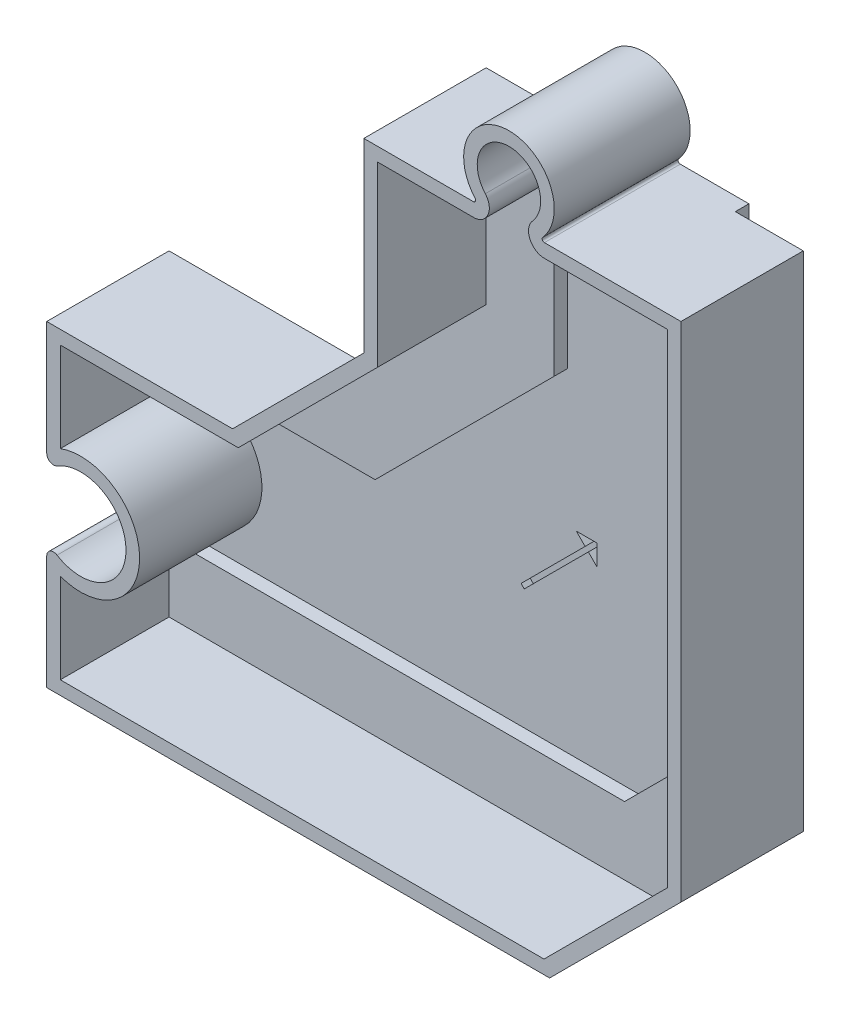
SolidWorks part; units mm, degrees
note: '?' marks a value the reader was unsure of.
material "ABS"
ref_plane "Plan de face" through (0, 0, 0) normal (0, 0, 1) x (1, 0, 0)
ref_plane "Plan de dessus" through (0, 0, 0) normal (0, 1, 0) x (1, 0, 0)
ref_plane "Plan de droite" through (0, 0, 0) normal (1, 0, 0) x (0, 0, -1)
sketch "Esquisse1" plane through (0, 0, 0) normal (0, 0, 1) x (1, 0, 0)
  line L0 (-32.0283, 105) -> (37.9717, 105)
  line L1 (37.9717, 105) -> (37.9717, -35)
  line L2 (37.9717, -35) -> (-102.0283, -35)
  line L3 (-102.0283, -35) -> (-102.0283, 35)
  line L4 (-102.0283, 35) -> (-32.0283, 35)
  line L5 (-32.0283, 35) -> (-32.0283, 105)
  line L6 (0, 105) -> (0, 0) construction
  line L7 (0, 0) -> (-102.0283, 0) construction
  dimension "D1" = 140
  dimension "D2" = 70
extrude "Boss.-Extru.1" add sketch "Esquisse1" along normal blind 30
chamfer "Chanfrein1" distance 28.99 angle 45 1 edges at (37.9717, -35, 15)
chamfer "Chanfrein2" distance 28.97 angle 45 1 edges at (-32.0283, 35, 15)
sketch3d "Esquisse3D3"
  line L0 (-87.0283, -20, 0) -> (2.7685, -20, 0)
  line L1 (-87.0283, 20, 0) -> (-87.0283, -20, 0)
  line L2 (-54.7851, 20, 0) -> (-87.0283, 20, 0)
  line L3 (-54.7851, 20, 0) -> (-17.0283, 57.7568, 0)
  line L4 (-17.0283, 90, 0) -> (-17.0283, 57.7568, 0)
  line L5 (22.9717, 90, 0) -> (-17.0283, 90, 0)
  line L6 (22.9717, 0.2032, 0) -> (22.9717, 90, 0)
  line L7 (22.9717, 0.2032, 0) -> (2.7685, -20, 0)
  line L8 (-102.0283, -20, 0) -> (2.7685, -20, 0)
  line L10 (-54.7851, 20, 0) -> (-102.0283, 20, 0)
  line L11 (-54.7851, 20, 0) -> (-17.0283, 57.7568, 0)
  line L12 (-17.0283, 105, 0) -> (-17.0283, 57.7568, 0)
  line L14 (22.9717, 0.2032, 0) -> (22.9717, 105, 0)
  line L15 (22.9717, 0.2032, 0) -> (2.7685, -20, 0)
  line L16 (-102.0283, 35, 0) -> (-102.0283, -35, 0) construction
  line L17 (37.9717, 105, 0) -> (-32.0283, 105, 0) construction
  line L18 (22.9717, 105, 0) -> (37.9717, 105, 0)
  line L19 (37.9717, 105, 0) -> (37.9717, -6.01, 0)
  line L20 (37.9717, -6.01, 0) -> (8.9817, -35, 0)
  line L21 (8.9817, -35, 0) -> (-102.0283, -35, 0)
  line L22 (-102.0283, -35, 0) -> (-102.0283, -20, 0)
  line L23 (-17.0283, 105, 0) -> (-32.0283, 105, 0)
  line L24 (-32.0283, 105, 0) -> (-32.0283, 63.97, 0)
  line L25 (-32.0283, 63.97, 0) -> (-60.9983, 35, 0)
  line L26 (-60.9983, 35, 0) -> (-102.0283, 35, 0)
  line L27 (-102.0283, 35, 0) -> (-102.0283, 20, 0)
  dimension "D1" = 15
extrude "Enlèv. mat.-Extru.3" cut sketch "Esquisse3D3" along direction (0, 0, -1) on the side against the normal blind 3
sketch "Esquisse4" plane through (0, 0, 0) normal (0, 0, -1) x (-1, 0, 0)
  line L1 (102.0283, 20) -> (102.0283, -20) construction
  circle A1 centre (94.5283, 0) radius 10
  dimension "D3" = 7.5
extrude "Enlèv. mat.-Extru.4" cut sketch "Esquisse4" against normal through all
sketch "Esquisse5" plane through (0, 0, 0) normal (0, 0, -1) x (-1, 0, 0)
  line L0 (-22.9717, 105) -> (17.0283, 105) construction
  circle A0 centre (0, 112.5) radius 10
  dimension "D1" = 20
  dimension "D2" = 7.5
extrude "Boss.-Extru.2" add sketch "Esquisse5" against normal blind 30
sketch "Esquisse6" plane through (0, 0, 0) normal (0, 0, -1) x (-1, 0, 0)
  line L0 (28.5625, 10.2847) -> (23.6128, 5.3349)
  line L1 (23.6128, 5.3349) -> (9.4707, 19.4771)
  line L2 (9.4707, 19.4771) -> (4.5209, 14.5273)
  line L3 (4.5209, 14.5273) -> (4.5209, 29.3766)
  line L4 (4.5209, 29.3766) -> (19.3701, 29.3766)
  line L5 (19.3701, 29.3766) -> (14.4204, 24.4268)
  line L6 (14.4204, 24.4268) -> (28.5625, 10.2847)
  dimension "D1" = 20
  dimension "D2" = 7
extrude "Boss.-Extru.3" add sketch "Esquisse6" along normal blind 2
fillet "Congé1" radius 1.5 2 edges at (-102.0283, 6.6144, 15) (-102.0283, -6.6144, 15)
fillet "Congé2" radius 0.5 2 edges at (-6.6144, 105, 15) (6.6144, 105, 15)
shell "Coque1" thickness 3
ref_axis "Axe1" through (37.9717, 105, 30) along (-0.7006, -0.7006, -0.1351)?
